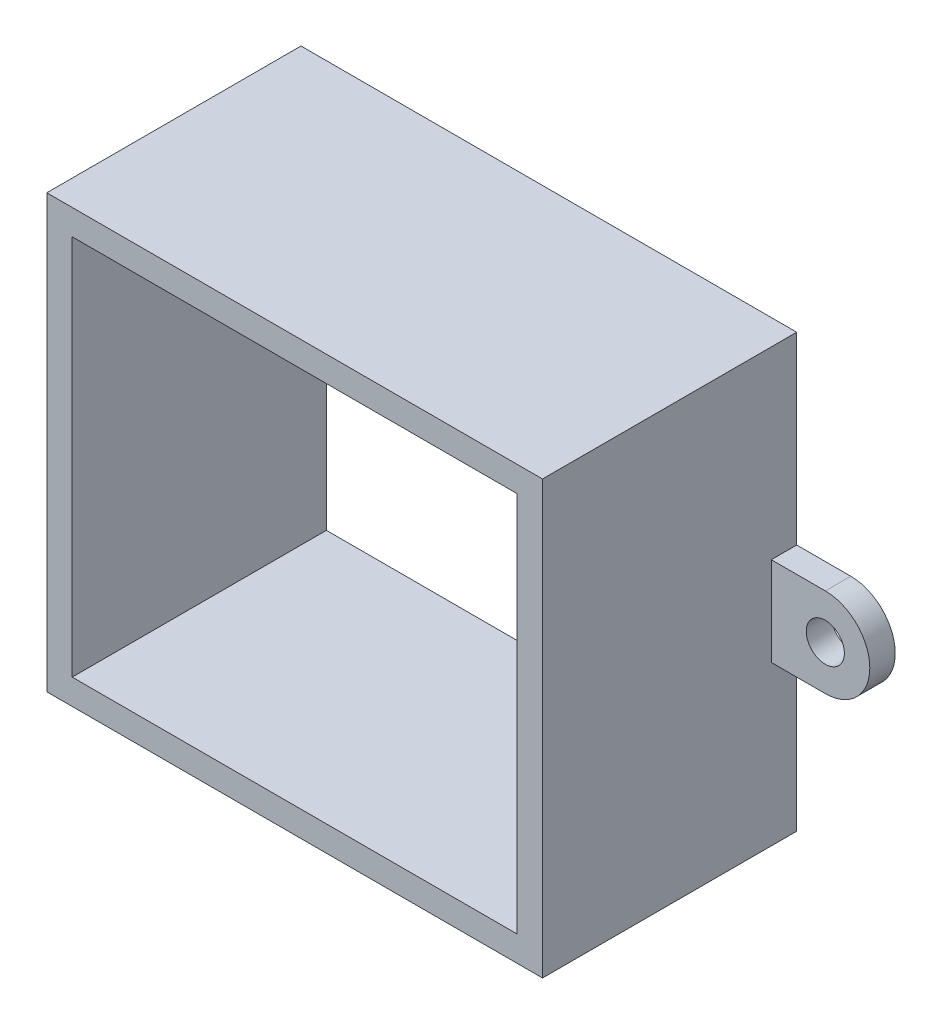
SolidWorks part; units mm, degrees
ref_plane "Front Plane" through (0, 0, 0) normal (0, 0, 1) x (1, 0, 0)
ref_plane "Top Plane" through (0, 0, 0) normal (0, 1, 0) x (1, 0, 0)
ref_plane "Right Plane" through (0, 0, 0) normal (1, 0, 0) x (0, 0, -1)
sketch "Sketch1" plane through (0, 0, 0) normal (0, 0, 1) x (1, 0, 0)
  line L0 (17.5, 14) -> (-6.25, 14) construction
  line L1 (0, 0) -> (35, 0)
  line L2 (0, 0) -> (0, 30)
  line L3 (0, 30) -> (35, 30)
  line L4 (35, 0) -> (35, 30)
  line L5 (-2, 32) -> (37, 32)
  line L6 (0, 27.1735) -> (-2, 27.1735) construction
  line L7 (-2, -2) -> (37, -2)
  line L8 (35, 27.1735) -> (37, 27.1735) construction
  line L9 (-2, 32) -> (-2, -2) construction
  line L10 (37, 32) -> (37, 0) construction
  line L11 (-2, 32) -> (-2, 17.5)
  line L12 (-2, 10.5) -> (-2, -2)
  line L13 (37, 32) -> (37, 17.5)
  line L14 (37, 10.5) -> (37, -2)
  line L15 (-6.25, 17.5) -> (-2, 17.5)
  line L16 (-6.25, 10.5) -> (-2, 10.5)
  line L17 (17.5, 14) -> (17.5, 34.6431) construction
  line L18 (41.25, 17.5) -> (37, 17.5)
  line L19 (41.25, 10.5) -> (37, 10.5)
  line L20 (-2, 10.5) -> (-2, 17.5)
  line L21 (37, 10.5) -> (37, 17.5)
  circle A0 centre (-6.25, 14) radius 1.5
  arc A1 (-6.25, 17.5) -> (-6.25, 10.5) centre (-6.25, 14) ccw
  arc A2 (41.25, 17.5) -> (41.25, 10.5) centre (41.25, 14) cw
  circle A3 centre (41.25, 14) radius 1.5
  dimension "D8" = 35
  dimension "D4" = 47.5
  dimension "D5" = 2
  dimension "D6" = 2
  dimension "D1" = 3
  dimension "D2" = 30
  dimension "D3" = 2
extrude "Boss-Extrude1" add sketch "Sketch1" along normal blind 20 contours L14 L21 L13 L5 L11 L20 L12 L7 L4 L1 L2 L3 region at (17.5, 31.4826, 0)
extrude "Boss-Extrude2" add sketch "Sketch1<3>" along normal blind 2 contours L15 A1 L16 L20 A0 | A2 L18 L21 L19 A3 region at (-2.1044, 14, 0) region at (39.125, 17.3956, 0)
sketch "Sketch1<3>" plane through (0, 0, 0) normal (0, 0, 1) x (1, 0, 0) same geometry as "Sketch1"
